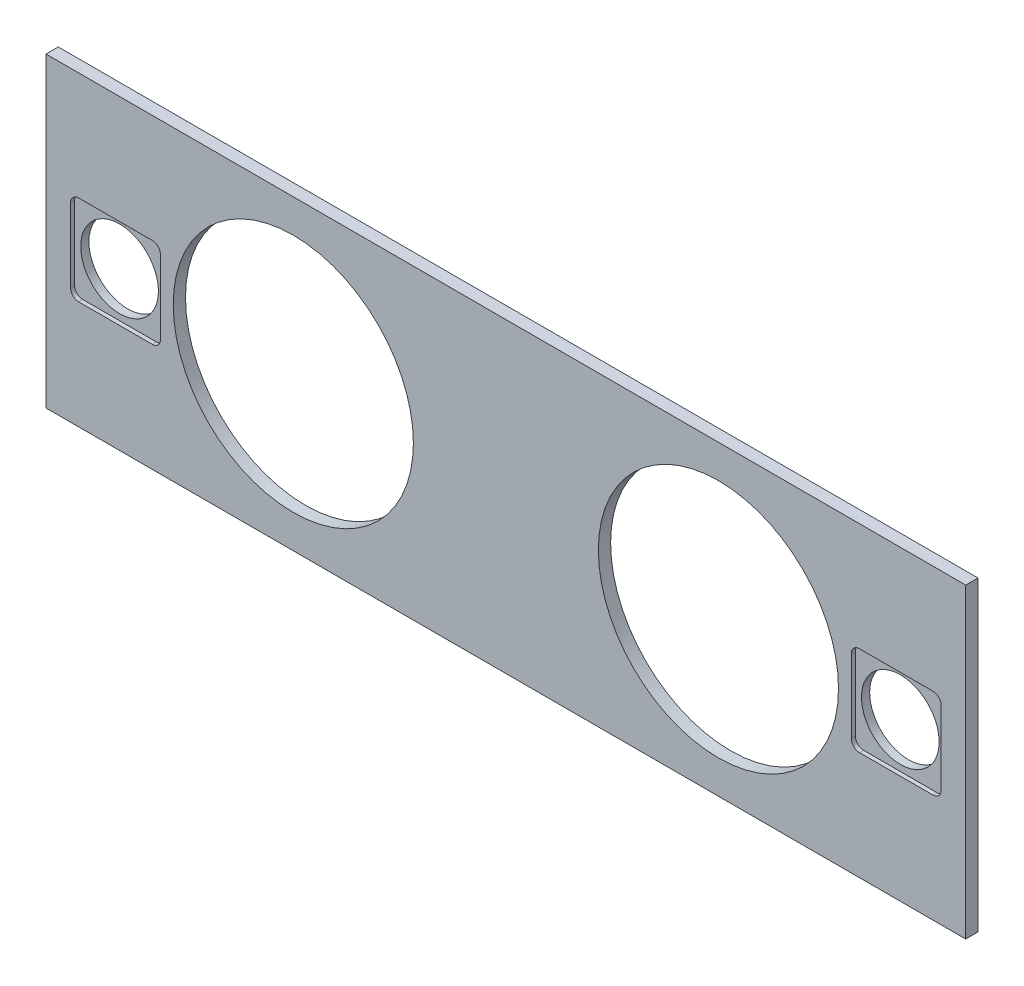
SolidWorks part; units mm, degrees
material "Pine"
ref_plane "Front Plane" through (0, 0, 0) normal (0, 0, 1) x (1, 0, 0)
ref_plane "Top Plane" through (0, 0, 0) normal (0, 1, 0) x (1, 0, 0)
ref_plane "Right Plane" through (0, 0, 0) normal (1, 0, 0) x (0, 0, -1)
sketch "Sketch1" plane through (0, 0, 0) normal (0, 0, 1) x (1, 0, 0)
  line L5 (450, 424.6951) -> (450, -112.2601) construction
  line L6 (0, 0) -> (900, 0)
  line L10 (0, 0) -> (0, 300)
  line L11 (0, 300) -> (900, 300)
  line L12 (900, 0) -> (900, 300)
  circle A0 centre (242, 150) radius 117.5
  circle A2 centre (658, 150) radius 117.5
  circle A3 centre (68, 150) radius 38
  circle A4 centre (832, 150) radius 38
  dimension "D1" = 235
  dimension "D8" = 76
  dimension "D2" = 900
  dimension "D3" = 300
  dimension "D4" = 242
  dimension "D5" = 150
  dimension "D6" = 68
  dimension "D7" = 150
  dimension "D9" = 242
extrude "Boss-Extrude1" add sketch "Sketch1" along normal blind 12 contours A2 | A0 | L10 L11 L12 L6 | A3 | A4 region at (658, 150, 0)
sketch "Sketch4" plane through (0, 0, 12) normal (0, 0, 1) x (1, 0, 0)
  line L0 (0, 0) -> (0, 300) construction
  line L1 (32, 194) -> (104, 194)
  line L2 (24, 186) -> (24, 114)
  line L3 (32, 106) -> (104, 106)
  line L4 (112, 186) -> (112, 114)
  line L5 (0, 0) -> (0, 300) construction
  line L6 (0, 300) -> (900, 300) construction
  line L7 (450, -84.0445) -> (450, 394.2312) construction
  line L8 (868, 106) -> (796, 106)
  line L9 (788, 186) -> (788, 114)
  line L10 (868, 194) -> (796, 194)
  line L11 (876, 186) -> (876, 114)
  arc A0 (104, 194) -> (112, 186) centre (104, 186) cw
  arc A1 (104, 106) -> (112, 114) centre (104, 114) ccw
  arc A2 (24, 114) -> (32, 106) centre (32, 114) ccw
  arc A3 (24, 186) -> (32, 194) centre (32, 186) cw
  arc A4 (796, 106) -> (788, 114) centre (796, 114) cw
  arc A5 (796, 194) -> (788, 186) centre (796, 186) ccw
  arc A6 (876, 114) -> (868, 106) centre (868, 114) cw
  arc A7 (876, 186) -> (868, 194) centre (868, 186) ccw
  point P16 (67.7235, 149.5451)
  dimension "D1" = 8
  dimension "D2" = 88
  dimension "D3" = 88
  dimension "D4" = 24
  dimension "D5" = 106
  dimension "D6" = 450
extrude "Cut-Extrude1" cut sketch "Sketch4" against normal blind 4 contours L2 A2 L3 A1 L4 A0 L1 A3 | L8 A4 L9 A5 L10 A7 L11 A6
equation "\"LENGTH\" = 900mm"
equation "\"D2@Sketch1\"=\"LENGTH\""
equation "\"D6@Sketch4\"=\"LENGTH\"/2"
equation "\"PLY\"= 12mm"
equation "\"D1@Boss-Extrude1\"=\"PLY\""
